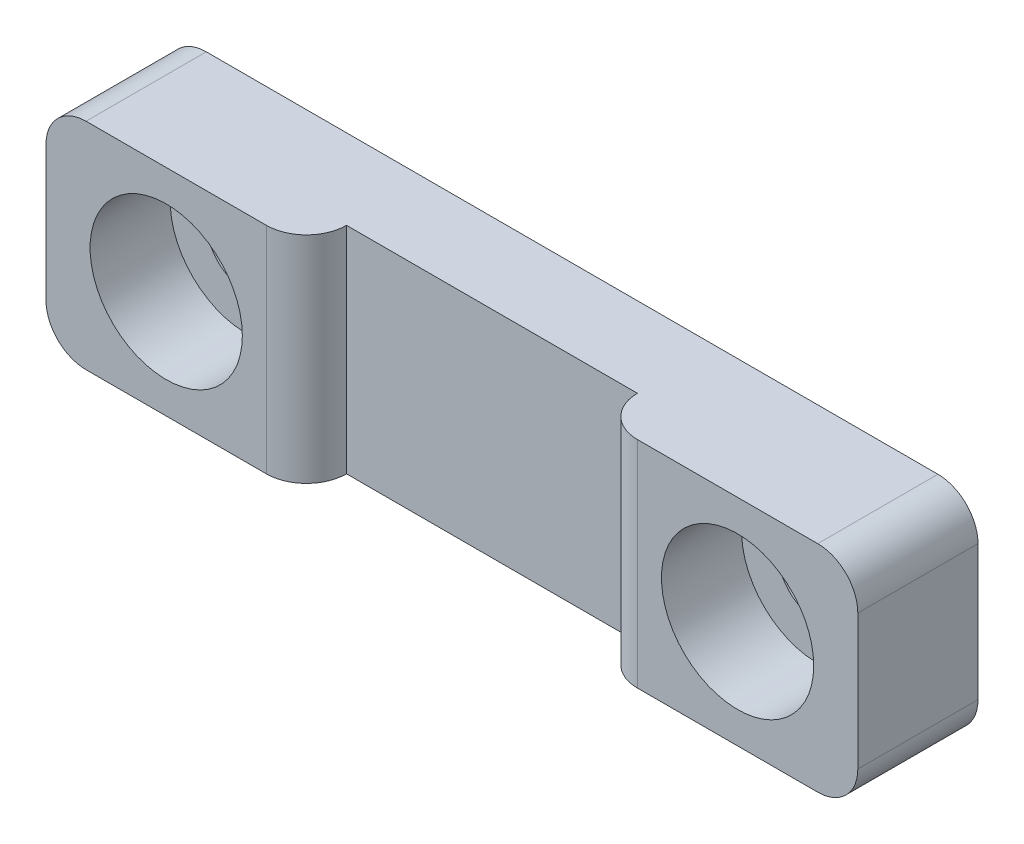
SolidWorks part; units mm, degrees
ref_plane "Front Plane" through (0, 0, 0) normal (0, 0, 1) x (1, 0, 0)
ref_plane "Top Plane" through (0, 0, 0) normal (0, 1, 0) x (1, 0, 0)
ref_plane "Right Plane" through (0, 0, 0) normal (1, 0, 0) x (0, 0, -1)
sketch "Sketch1" plane through (0, 0, 0) normal (0, 0, 1) x (1, 0, 0)
  line L0 (-7.0701, 2.6858) -> (25.3872, 2.6858) construction
  line L1 (1, 0) -> (19.26, 0)
  line L2 (0, 1) -> (0, 4.3717)
  line L3 (1, 5.3717) -> (19.26, 5.3717)
  line L4 (20.26, 1) -> (20.26, 4.3717)
  circle A0 centre (3, 2.6858) radius 1.9
  circle A1 centre (17.26, 2.6858) radius 1.9
  arc A2 (19.26, 0) -> (20.26, 1) centre (19.26, 1) ccw
  arc A3 (19.26, 5.3717) -> (20.26, 4.3717) centre (19.26, 4.3717) cw
  arc A4 (1, 0) -> (0, 1) centre (1, 1) cw
  arc A5 (0, 4.3717) -> (1, 5.3717) centre (1, 4.3717) cw
  point P17 (0, 0)
  dimension "D1" = 3.8
  dimension "D4" = 1
  dimension "D2" = 14.26
  dimension "D3" = 3
  dimension "D5" = 3
extrude "Boss-Extrude1" add sketch "Sketch1" along normal blind 2
sketch "Sketch2" plane through (0, 0, 0) normal (0, 0, -1) x (-1, 0, 0)
  line L4 (-19.26, 0) -> (-1, 0)
  line L5 (0, 1) -> (0, 4.3717)
  line L6 (-1, 5.3717) -> (-19.26, 5.3717)
  line L7 (-20.26, 4.3717) -> (-20.26, 1)
  line L8 (-19.26, 0) -> (-1, 0)
  line L9 (0, 1) -> (0, 4.3717)
  line L10 (-1, 5.3717) -> (-19.26, 5.3717)
  line L11 (-20.26, 4.3717) -> (-20.26, 1)
  circle A0 centre (-17.26, 2.6858) radius 1
  circle A1 centre (-3, 2.6858) radius 1
  arc A4 (-20.26, 1) -> (-19.26, 0) centre (-19.26, 1) ccw
  arc A5 (-1, 0) -> (0, 1) centre (-1, 1) ccw
  arc A6 (0, 4.3717) -> (-1, 5.3717) centre (-1, 4.3717) ccw
  arc A7 (-19.26, 5.3717) -> (-20.26, 4.3717) centre (-19.26, 4.3717) ccw
  arc A8 (-20.26, 1) -> (-19.26, 0) centre (-19.26, 1) ccw
  arc A9 (-1, 0) -> (0, 1) centre (-1, 1) ccw
  arc A10 (0, 4.3717) -> (-1, 5.3717) centre (-1, 4.3717) ccw
  arc A11 (-19.26, 5.3717) -> (-20.26, 4.3717) centre (-19.26, 4.3717) ccw
  dimension "D2" = 2
  dimension "D1" = 0
extrude "Boss-Extrude2" add sketch "Sketch2" along normal blind 1
sketch "Sketch3" plane through (0, 0, 0) normal (0, -1, 0) x (1, 0, 0)
  line L0 (0, 2) -> (0, -1) construction
  line L1 (6.5, 3.9912) -> (13.76, 3.9912)
  line L2 (6.5, 3.9912) -> (6.5, 1)
  line L3 (6.5, 1) -> (13.76, 1)
  line L4 (13.76, 3.9912) -> (13.76, 1)
  line L5 (20.26, 2) -> (20.26, -1) construction
  line L6 (1, 2) -> (19.26, 2) construction
  dimension "D1" = 6.5
  dimension "D2" = 6.5
  dimension "D3" = 1
extrude "Cut-Extrude1" cut sketch "Sketch3" against normal blind 10
fillet "Fillet1" radius 1 2 edges at (13.76, 2.6858, 2) (6.5, 2.6858, 2)
